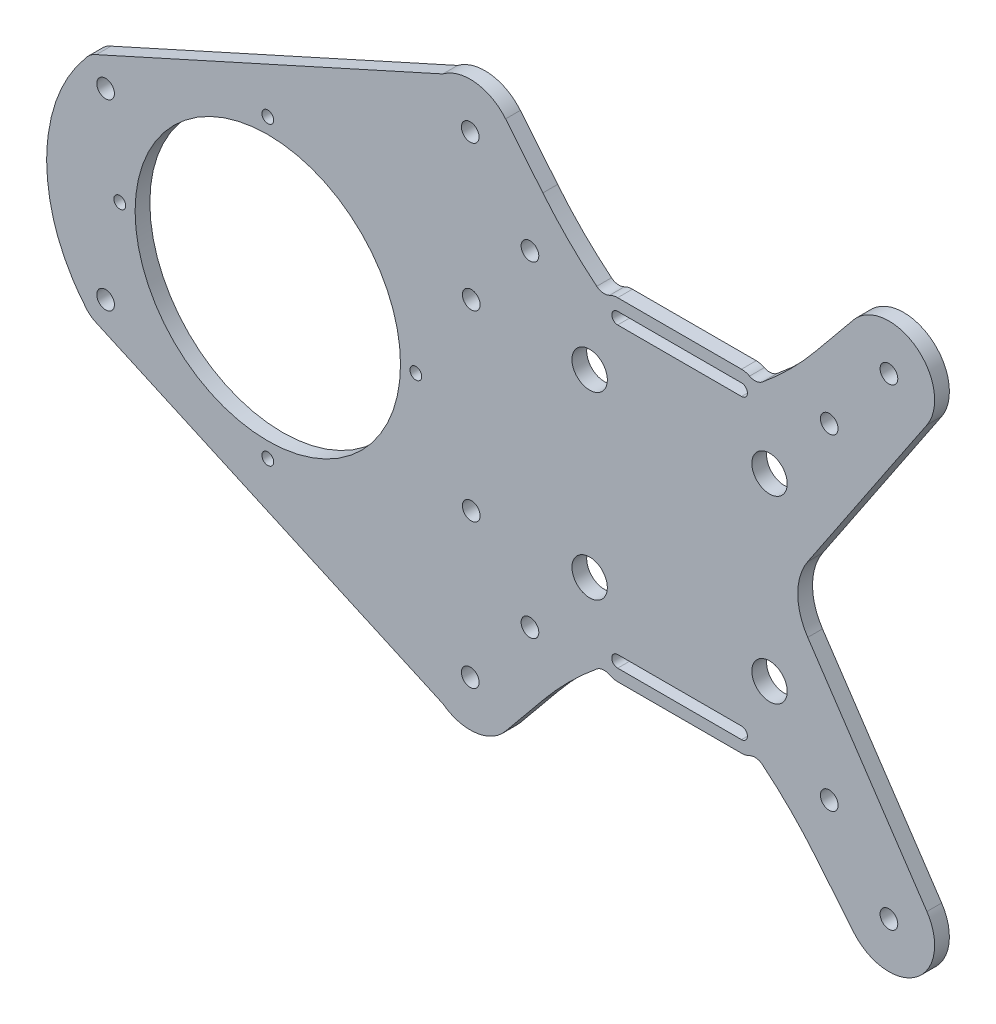
SolidWorks part; units mm, degrees
ref_plane "Alzado" through (0, 0, 0) normal (0, 0, 1) x (1, 0, 0)
ref_plane "Planta" through (0, 0, 0) normal (0, 1, 0) x (1, 0, 0)
ref_plane "Vista lateral" through (0, 0, 0) normal (1, 0, 0) x (0, 0, -1)
sketch "Croquis1" plane through (0, 0, 0) normal (0, 0, 1) x (1, 0, 0)
  line L0 (-29.5025, -44.95) -> (-23.1778, -37.2438)
  line L1 (29.5025, 44.95) -> (23.1778, 37.2438)
  line L2 (-10.5003, 28.196) -> (10.5003, 28.196)
  line L3 (10.4997, -24.196) -> (-10.5003, -24.196)
  line L4 (10.4997, 24.196) -> (-10.5003, 24.196)
  line L5 (23.1779, -37.2437) -> (29.5025, -44.95)
  line L6 (41.9317, 35.7196) -> (21.7292, 5.5661)
  line L7 (-10.5003, -28.196) -> (10.4997, -28.196)
  line L8 (-85.5141, -4.166) -> (-47.6698, -4.166) construction
  line L9 (-85.5141, 4.166) -> (-47.6698, 4.166) construction
  line L10 (-97.3181, -20) -> (-50.1355, -20)
  line L11 (-23.1779, 37.2437) -> (-29.5025, 44.95)
  line L12 (41.9317, -35.7196) -> (21.7292, -5.5661)
  line L13 (-97.3181, 20) -> (-50.1355, 20)
  line L14 (-10.5003, -26.196) -> (10.4997, -26.196)
  line L15 (-10.5003, 26.196) -> (10.4997, 26.196)
  arc A0 (21.7292, 5.5661) -> (21.7292, -5.5661) centre (30.037, 0) ccw
  circle A1 centre (-25.3716, 27.6416) radius 2.25
  arc A2 (41.9317, 35.7196) -> (29.5025, 44.95) centre (35.4932, 40.0333) ccw
  arc A3 (-41.8863, -35.6526) -> (-29.5025, -44.95) centre (-35.4932, -40.0333) ccw
  circle A4 centre (-35.4932, 40.0333) radius 2.25
  arc A5 (-41.8863, -35.6526) -> (-50.1355, -20) centre (-50.1355, -30) ccw
  circle A6 centre (-35.4932, -40.0333) radius 2.25
  arc A7 (14.0461, 28.0999) -> (23.1778, 37.2438) centre (-27.1528, 78.3757) ccw
  circle A8 centre (15.25, -15.25) radius 3
  arc A9 (-14.0461, 28.0999) -> (-11.8672, 27.8665) centre (-12.7784, 29.6469) ccw
  circle A10 centre (35.4932, -40.0333) radius 2.25
  arc A11 (14.0461, -28.0999) -> (11.8672, -27.8665) centre (12.7784, -29.6469) ccw
  circle A12 centre (-15.25, 15.25) radius 3
  arc A13 (10.4997, 24.196) -> (10.4997, 26.196) centre (10.4997, 25.196) ccw
  arc A14 (-47.6698, 4.166) -> (-46.6061, 8.9284) centre (-47.6698, 6.666) ccw construction
  circle A15 centre (-25.3716, -27.6416) radius 2.25
  arc A16 (-48.7757, -9.4863) -> (-46.6061, -8.9284) centre (-49.1589, -3.4986) ccw construction
  circle A17 centre (-35.3181, 15.5) radius 1.5
  arc A18 (-11.8672, -27.8665) -> (-10.5003, -28.196) centre (-10.5003, -25.196) ccw
  circle A19 centre (25.3716, -27.6416) radius 2.25
  arc A20 (-14.0461, -28.0999) -> (-23.1778, -37.2438) centre (27.1528, -78.3757) ccw
  arc A21 (29.5025, -44.95) -> (41.9317, -35.7196) centre (35.4932, -40.0333) ccw
  arc A22 (11.8672, 27.8665) -> (14.0461, 28.0999) centre (12.7784, 29.6469) ccw
  arc A23 (10.4997, -28.196) -> (11.8672, -27.8665) centre (10.5003, -25.196) ccw
  arc A24 (-10.5003, -24.196) -> (-10.5003, -26.196) centre (-10.5003, -25.196) ccw
  circle A25 centre (-15.25, -15.25) radius 3
  circle A26 centre (-97.3181, 15.5) radius 1.5
  arc A27 (-46.6061, -8.9284) -> (-47.6698, -4.166) centre (-47.6698, -6.666) ccw construction
  circle A28 centre (15.25, 15.25) radius 3
  arc A29 (-50.1355, 20) -> (-41.8863, 35.6526) centre (-50.1355, 30) ccw
  arc A30 (-11.8672, -27.8665) -> (-14.0461, -28.0999) centre (-12.7784, -29.6469) ccw
  circle A31 centre (-35.3181, -15.5) radius 1.5
  arc A32 (-10.5003, 26.196) -> (-10.5003, 24.196) centre (-10.5003, 25.196) ccw
  circle A33 centre (25.3716, 27.6416) radius 2.25
  arc A34 (-88.511, 7.03) -> (-85.5141, 4.166) centre (-85.5141, 7.166) ccw construction
  arc A35 (-88.511, -7.03) -> (-81.5427, -13.2223) centre (-82.5172, -7.302) ccw construction
  arc A36 (-10.5003, 28.196) -> (-11.8672, 27.8665) centre (-10.5003, 25.196) ccw
  circle A37 centre (-97.3181, -15.5) radius 1.5
  arc A38 (-97.3181, 20) -> (-100.6815, 18.3128) centre (-97.3181, 15.804) ccw
  arc A39 (-81.5427, 13.2223) -> (-48.7757, 9.4863) centre (-27.5409, 341.2912) ccw construction
  arc A40 (-81.5427, 13.2223) -> (-88.511, 7.03) centre (-82.5172, 7.302) ccw construction
  arc A41 (11.8672, 27.8665) -> (10.5003, 28.196) centre (10.5003, 25.196) ccw
  arc A42 (-48.7757, -9.4863) -> (-81.5427, -13.2223) centre (-27.5408, -341.2912) ccw construction
  arc A43 (-85.5141, -4.166) -> (-88.511, -7.03) centre (-85.5141, -7.166) ccw construction
  arc A44 (23.1779, -37.2437) -> (14.0461, -28.0999) centre (-27.1523, -78.3761) ccw
  circle A45 centre (35.4932, 40.0333) radius 2.25
  arc A46 (-46.6061, 8.9284) -> (-48.7757, 9.4863) centre (-49.1589, 3.4986) ccw construction
  arc A47 (10.4997, -26.196) -> (10.4997, -24.196) centre (10.4997, -25.196) ccw
  arc A48 (-29.5025, 44.95) -> (-41.8863, 35.6526) centre (-35.4932, 40.0333) ccw
  arc A49 (-23.1779, 37.2437) -> (-14.0461, 28.0999) centre (27.1523, 78.3761) ccw
  arc A50 (-100.6815, -18.3128) -> (-97.3181, -20) centre (-97.3181, -15.804) ccw
  spline S0 degree 3 poles (-107.3181, 0) (-107.2524, 7.0597) (-104.9757, 13.1646) (-100.6815, 18.3128) knots 0 0 0 0 1 1 1 1
  spline S1 degree 3 poles (-107.3181, 0) (-107.2524, -7.0597) (-104.9757, -13.1646) (-100.6815, -18.3128) knots 0 0 0 0 1 1 1 1
extrude "Saliente-Extruir1" add sketch "Croquis1" along normal blind 2.5
sketch "Croquis6" plane through (0, 0, 2.5) normal (0, 0, 1) x (1, 0, 0)
  line L0 (-99.1995, 19.5546) -> (-40.1463, 46.231)
  line L2 (-107.3181, 0) -> (-91.4281, 0) construction
  line L8 (-50.1355, 20) -> (-97.3181, 20)
  line L11 (-50.1355, -20) -> (-97.3181, -20)
  line L12 (-99.1995, -19.5546) -> (-40.1463, -46.231)
  line L13 (0, 0) -> (0, 40.0333) construction
  line L14 (0, 0) -> (37.562, 0) construction
  arc A2 (-29.5025, 44.95) -> (-41.8863, 35.6526) centre (-35.4932, 40.0333) ccw construction
  arc A3 (-40.1463, 46.231) -> (-41.8863, 35.6526) centre (-35.4932, 40.0333) ccw
  arc A7 (-97.3181, 20) -> (-100.6815, 18.3128) centre (-97.3181, 15.804) ccw construction
  arc A12 (-50.1355, 20) -> (-41.8863, 35.6526) centre (-50.1355, 30) ccw
  arc A16 (-99.1995, 19.5546) -> (-97.3181, 20) centre (-98.7978, 22.0539) ccw
  arc A17 (-99.1995, -19.5546) -> (-97.3181, -20) centre (-98.7978, -22.0539) cw
  arc A18 (-50.1355, -20) -> (-41.8863, -35.6526) centre (-50.1355, -30) cw
  arc A19 (-40.1463, -46.231) -> (-41.8863, -35.6526) centre (-35.4932, -40.0333) cw
  circle A20 centre (-35.4932, 40.0333) radius 2.25
  circle A21 centre (-35.4932, 40.0333) radius 1.5
  circle A22 centre (-25.3716, 27.6416) radius 2.25
  circle A23 centre (-25.3716, 27.6416) radius 1.5
  circle A24 centre (25.3716, 27.6416) radius 1.5
  circle A25 centre (25.3716, 27.6416) radius 2.25
  circle A26 centre (35.4932, 40.0333) radius 1.5
  circle A27 centre (35.4932, 40.0333) radius 2.25
  circle A28 centre (35.4932, -40.0333) radius 2.25
  circle A29 centre (35.4932, -40.0333) radius 1.5
  circle A30 centre (25.3716, -27.6416) radius 2.25
  circle A31 centre (25.3716, -27.6416) radius 1.5
  circle A32 centre (-25.3716, -27.6416) radius 1.5
  circle A33 centre (-25.3716, -27.6416) radius 2.25
  circle A34 centre (-35.4932, -40.0333) radius 1.5
  circle A35 centre (-35.4932, -40.0333) radius 2.25
  dimension "D1" = 3
  dimension "D2" = 3
extrude "Saliente-Extruir3" add sketch "Croquis6" against normal up to vertex (2.5 mm away) up to point (-50.1355, -20, 0)
sketch "Croquis5" plane through (0, 0, 2.5) normal (0, 0, 1) x (1, 0, 0)
  line L0 (-92.3181, 0) -> (-107.3181, 0) construction
  line L1 (-46.8181, 0) -> (-46.8181, -15) construction
  line L2 (-102.3181, -32.5) -> (-37.3181, -32.5) construction
  line L3 (-102.3181, -32.5) -> (-102.3181, 32.5) construction
  line L4 (-102.3181, 32.5) -> (-37.3181, 32.5) construction
  line L5 (-37.3181, -32.5) -> (-37.3181, 32.5) construction
  line L6 (-102.3181, -32.5) -> (-37.3181, 32.5) construction
  line L7 (-102.3181, 32.5) -> (-37.3181, -32.5) construction
  line L8 (-46.8181, -15) -> (-42.8181, -15) construction
  line L9 (-42.8181, -15) -> (-42.8181, 15) construction
  line L10 (-42.8181, 15) -> (-46.8181, 15) construction
  line L11 (-46.8181, 15) -> (-46.8181, 0) construction
  line L12 (-54.8181, -27) -> (-84.8181, -27) construction
  line L13 (-69.8181, 0) -> (-37.3181, 0) construction
  line L14 (-45.7181, 0) -> (-47.3181, 0) construction
  line L15 (-47.3181, 0) -> (-46.3181, 0) construction
  circle A0 centre (-69.8181, 0) radius 22.5
  circle A1 centre (-44.8181, 13) radius 1 construction
  circle A2 centre (-44.8181, -13) radius 1 construction
  circle A3 centre (-56.8181, -25) radius 1 construction
  circle A4 centre (-82.8181, -25) radius 1 construction
  circle A5 centre (-94.8181, -13) radius 1 construction
  circle A6 centre (-94.8181, 13) radius 1 construction
  circle A7 centre (-82.8181, 25) radius 1 construction
  circle A8 centre (-56.8181, 25) radius 1 construction
  circle A9 centre (-44.7181, 0) radius 1
  circle A11 centre (-44.7181, 0) radius 1.6 construction
  circle A12 centre (-69.8181, -25.1) radius 1
  circle A13 centre (-94.9181, 0) radius 1
  circle A14 centre (-69.8181, 25.1) radius 1
  point P32 (-69.8181, 0)
  point P49 (-69.8181, 0)
  dimension "D1" = 45
  dimension "D9" = 2
  dimension "D10" = 2
  dimension "D12" = 2
  dimension "D14" = 1
  dimension "D15" = 2
  dimension "D16" = 3.2
  dimension "D2" = 15
  dimension "D3" = 65
  dimension "D4" = 65
  dimension "D5" = 23
  dimension "D6" = 4
  dimension "D7" = 15
  dimension "D8" = 15
  dimension "D11" = 2
  dimension "D13" = 4
  dimension "D17" = 4
extrude "Cortar-Extruir5" cut sketch "Croquis5" against normal up to vertex (2.5 mm away) up to point (-100.6815, -18.3128, 0)
sketch "Croquis7" [suppressed] plane through (0, 0, 2.5) normal (0, 0, 1) x (1, 0, 0)
  line L0 (-94.8181, 13) -> (-94.8181, -13) construction
  line L1 (-94.8181, -13) -> (-92.3181, -13) construction
  line L2 (-94.8181, 13) -> (-95.2639, 10.5401) construction
  line L3 (-94.8181, -13) -> (-94.8181, -15.5) construction
  line L4 (-94.8181, -15.5) -> (-74.7678, -15.5)
  line L5 (-74.7678, -15.5) -> (-74.7678, -4.9497)
  line L6 (-74.7678, -4.9497) -> (-100.2237, -4.9497)
  line L7 (-100.2237, -4.9497) -> (-100.2237, -19.0919)
  line L8 (-98.8886, -19.695) -> (-40.1463, -46.231) construction
  line L9 (-100.2237, -19.0919) -> (-77.4195, -29.3934)
  line L10 (-77.4195, -29.3934) -> (-94.8181, -15.5)
  circle A0 centre (-94.8181, 13) radius 1.6
  circle A1 centre (-94.8181, -13) radius 1.6
  dimension "D4" = 3.2
  dimension "D5" = 3.2
  dimension "D1" = 2.5
  dimension "D2" = 2.5
  dimension "D3" = 2.5
sketch "Croquis8" plane through (0, 0, 2.5) normal (0, 0, 1) x (1, 0, 0)
  line L0 (-96.5181, 0) -> (-97.5181, 0) construction
  circle A0 centre (-69.8181, 0) radius 22.5
  circle A1 centre (-69.8181, 0) radius 27.7
  circle A2 centre (-97.3181, -15.5) radius 2.5 construction
  circle A3 centre (-69.8181, 25.1) radius 1.6
  circle A4 centre (-94.9181, 0) radius 1.6
  circle A5 centre (-44.7181, 0) radius 1.6
  circle A6 centre (-69.8181, -25.1) radius 1.6
  point P21 (-69.8181, 0)
  dimension "D1" = 1
  dimension "D2" = 3.2
  dimension "D3" = 5
  dimension "D4" = 45
  dimension "D5" = 4
  dimension "D6" = 55.4
sketch "Croquis9" plane through (0, 0, 2.5) normal (0, 0, 1) x (1, 0, 0)
  circle A0 centre (-97.3181, 15.5) radius 1.5
  circle A1 centre (-97.3181, -15.5) radius 1.5
  circle A2 centre (-35.3181, -15.5) radius 1.5
  circle A3 centre (-35.3181, 15.5) radius 1.5
